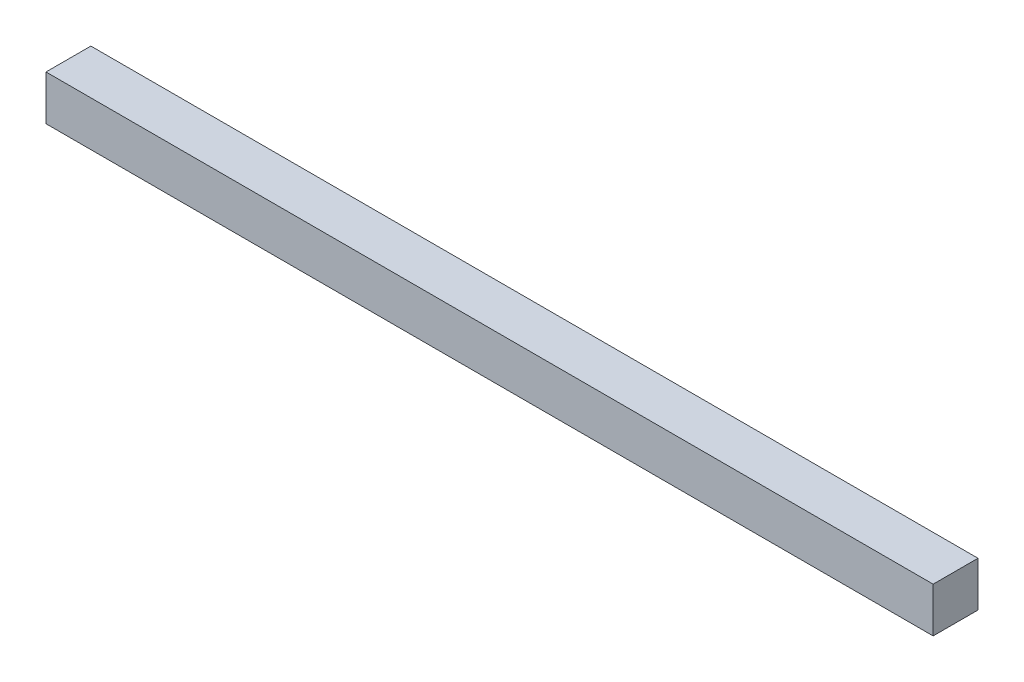
SolidWorks part; units mm, degrees
ref_plane "Front Plane" through (0, 0, 0) normal (0, 0, 1) x (1, 0, 0)
ref_plane "Top Plane" through (0, 0, 0) normal (0, 1, 0) x (1, 0, 0)
ref_plane "Right Plane" through (0, 0, 0) normal (1, 0, 0) x (0, 0, -1)
sketch "Sketch1" plane through (0, 0, 0) normal (0, 0, 1) x (1, 0, 0)
  line L0 (-89, 0) -> (89, 0) construction
  line L1 (0, -27.7067) -> (0, 27.7067) construction
  dimension "D1" = 178
sketch "Sketch2" plane through (0, 0, 0) normal (1, 0, 0) x (0, 0, -1)
  line L1 (-4.5, -4.5) -> (4.5, -4.5)
  line L2 (-4.5, -4.5) -> (-4.5, 4.5)
  line L3 (-4.5, 4.5) -> (4.5, 4.5)
  line L4 (4.5, -4.5) -> (4.5, 4.5)
  line L5 (-4.5, -4.5) -> (4.5, 4.5) construction
  line L6 (-4.5, 4.5) -> (4.5, -4.5) construction
  point P0 (0, 0)
  dimension "D1" = 9
extrude "Boss-Extrude1" add sketch "Sketch2" along normal up to vertex (89 mm away) and the other way up to vertex (89 mm away) up to point (89, 0, 0) other way up to point (-89, 0, 0)
